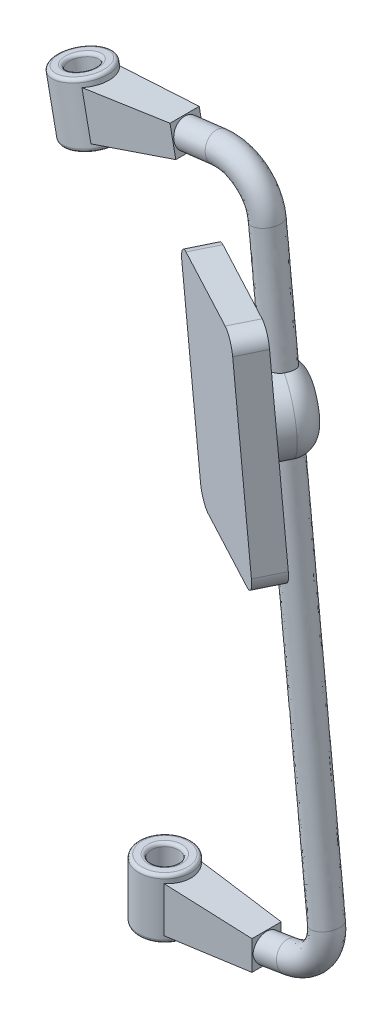
SolidWorks part; units mm, degrees
ref_plane "Front Plane" through (0, 0, 0) normal (0, 0, 1) x (1, 0, 0)
ref_plane "Top Plane" through (0, 0, 0) normal (0, 1, 0) x (1, 0, 0)
ref_plane "Right Plane" through (0, 0, 0) normal (1, 0, 0) x (0, 0, -1)
sketch "Sketch1" plane through (0, 0, 0) normal (0, 1, 0) x (1, 0, 0)
  circle A0 centre (0, 0) radius 12.5
  circle A1 centre (0, 0) radius 24
  dimension "D1" = 25
  dimension "D2" = 48
extrude "Boss-Extrude1" add sketch "Sketch1" along normal mid plane 55 contours A1 | A0
fillet "Fillet1" radius 3 4 edges at (0, 27.5, 12.5) (0, 27.5, 24) (0, -27.5, 12.5) (0, -27.5, 24)
ref_plane "Plane1" through (15, 0, 0) normal (1, 0, 0) x (0, 0, -1)
sketch "Sketch4" plane through (15, 0, 0) normal (1, 0, 0) x (0, 0, -1)
  line L0 (-20.6117, 0) -> (41.9806, 0) construction
  line L1 (0, 23.0094) -> (0, -24.2714) construction
  line L3 (-17.5, 21) -> (17.5, 21)
  line L4 (-17.5, 21) -> (-17.5, -21)
  line L5 (-17.5, -21) -> (17.5, -21)
  line L6 (17.5, 21) -> (17.5, -21)
  circle A0 centre (0, 0) radius 12.5
  dimension "D1" = 25
  dimension "D2" = 42
  dimension "D3" = 35
sketch "Sketch6" plane through (0, 0, 0) normal (0, 0, 1) x (1, 0, 0)
  line L0 (94, 0) -> (-270.3195, 0) construction
  line L1 (0, -79.4187) -> (0, 200.8809) construction
  line L2 (-40, -137.5526) -> (-40, 194) construction
  line L3 (-40, 194) -> (-114.1897, 559.2311) construction
  line L4 (-40, 194) -> (-40, 202.5264) construction
  line L6 (15.5, 27.5) -> (-15.5, 27.5) construction
  line L7 (-65.6804, 569.0848) -> (-65.6804, 254.5249) construction
  line L8 (-114.1897, 559.2311) -> (-65.6804, 569.0848) construction
  line L9 (24, -24.5) -> (24, 24.5) construction
  line L10 (-206.2715, 568.588) -> (20.964, 614.7466) construction
  line L11 (-65.6804, 569.0848) -> (-84.3739, 661.1117) construction
  dimension "D1" = 40
  dimension "D2" = 372.69
  dimension "D3" = 11.482
  dimension "D4" = 166.5
  dimension "D5" = 49.5
  dimension "D6" = 70
  dimension "D7" = 27.5
  dimension "D8" = 94
  dimension "D9" = 94
ref_plane "Plane2" through (-65.6804, 569.0848, 0) normal (-0.1991, 0.98, 0) x (0.98, 0.1991, 0)
sketch "Sketch8" plane through (-65.6804, 569.0848, 0) normal (-0.1991, 0.98, 0) x (0.98, 0.1991, 0)
  circle A0 centre (0, 0) radius 24
  circle A1 centre (0, 0) radius 12.5
  dimension "D1" = 25
  dimension "D2" = 48
extrude "Boss-Extrude2" add sketch "Sketch8" along normal blind 55 separate body
fillet "Fillet2" radius 3 4 edges at (-100.1487, 618.2065, 0) (-88.8788, 620.4957, 0) (-89.2001, 564.3072, 0) (-77.9302, 566.5965, 0)
ref_plane "Plane3" through (94, 0, 0) normal (1, 0, 0) x (0, 0, -1)
sketch "Sketch11" plane through (94, 0, 0) normal (1, 0, 0) x (0, 0, -1)
  line L0 (-26.258, 0) -> (32.0372, 0) construction
  line L1 (-13.5, 13.5) -> (13.5, 13.5)
  line L2 (-13.5, 13.5) -> (-13.5, -13.5)
  line L3 (-13.5, -13.5) -> (13.5, -13.5)
  line L4 (13.5, 13.5) -> (13.5, -13.5)
  line L5 (0, 21.6136) -> (0, -31.9549) construction
  line L6 (0, -137.5526) -> (0, 194) construction
  dimension "D1" = 27
  dimension "D2" = 27
loft "Loft1" add section "Sketch4" section "Sketch11"
ref_plane "Plane4" through (47.9402, 9.7381, 0) normal (0.98, 0.1991, 0) x (0, 0, -1)
ref_plane "Plane5" through (62.64, 12.7241, 0) normal (0.98, 0.1991, 0) x (0, 0, -1)
sketch "Sketch14" plane through (62.64, 12.7241, 0) normal (0.98, 0.1991, 0) x (0, 0, -1)
  line L0 (-40.0874, 598.2699) -> (54.1514, 598.2699) construction
  line L1 (0, 629.9205) -> (0, 567.8792) construction
  line L4 (24, 622.7699) -> (-24, 622.7699) construction
  line L5 (-24, 573.7699) -> (24, 573.7699) construction
  line L6 (-24, 622.7699) -> (-24, 573.7699) construction
  line L7 (24, 573.7699) -> (24, 622.7699) construction
  line L9 (-17.5, 619.2699) -> (17.5, 619.2699)
  line L10 (-17.5, 619.2699) -> (-17.5, 577.2699)
  line L11 (-17.5, 577.2699) -> (17.5, 577.2699)
  line L12 (17.5, 619.2699) -> (17.5, 577.2699)
  circle A0 centre (0, 598.2699) radius 12.5
  dimension "D1" = 25
  dimension "D2" = 42
  dimension "D3" = 35
ref_plane "Plane6" through (20.964, 614.7466, 0) normal (0.98, 0.1991, 0) x (0, 0, -1)
sketch "Sketch15" plane through (20.964, 614.7466, 0) normal (0.98, 0.1991, 0) x (0, 0, -1)
  line L1 (-13.5, 13.5) -> (13.5, 13.5)
  line L2 (-13.5, 13.5) -> (-13.5, -13.5)
  line L3 (-13.5, -13.5) -> (13.5, -13.5)
  line L4 (13.5, 13.5) -> (13.5, -13.5)
  line L5 (-40.0874, 0) -> (54.1514, 0) construction
  line L6 (0, 18.0247) -> (0, -17.7591) construction
  line L7 (0, -27.5) -> (0, 66.4063) construction
  dimension "D1" = 27
  dimension "D2" = 27
loft "Loft2" add section "Sketch14" section "Sketch15"
sketch "Sketch16" plane through (0, 0, 0) normal (0, 0, 1) x (1, 0, 0)
  line L0 (20.964, 614.7466) -> (50.0307, 618.2474)
  line L1 (94.6061, 582.6051) -> (149.3849, 47.1347)
  line L3 (116.018, 3.5834) -> (94, 0)
  arc A0 (50.0307, 618.2474) -> (94.6061, 582.6051) centre (54.8138, 578.5344) cw
  arc A1 (149.3849, 47.1347) -> (116.018, 3.5834) centre (109.5926, 43.0639) cw
  point P16 (90.4617, 623.1169)
  point P19 (153.2208, 9.6381)
  dimension "D3" = 40
  dimension "D1" = 70
  dimension "D2" = 60
sketch "Sketch17" plane through (140.0589, 28.4503, 0) normal (0.98, 0.1991, 0) x (0, 0, -1)
  circle A0 centre (0, 598.2699) radius 12.5
  dimension "D1" = 25
sweep "Sweep2" add profiles "Sketch17" path "Sketch16"
sketch "Sketch18" plane through (0, 0, 0) normal (0, 0, 1) x (1, 0, 0)
  line L0 (84.3257, 683.0971) -> (163.998, -95.7106) construction
  line L1 (161.6774, 49.4032) -> (106.8985, 584.8736) construction
  line L2 (82.3137, 580.3367) -> (137.0925, 44.8663) construction
ref_plane "Plane8" through (38.1524, 3.903, -66.4268) normal (-0.4974, -0.0509, 0.866) x (0.1018, -0.9948, 0)
sketch "Sketch20" plane through (38.1524, 3.903, -66.4268) normal (-0.4974, -0.0509, 0.866) x (0.1018, -0.9948, 0)
  line L0 (-670.9687, 132.8536) -> (111.9037, 132.8536) construction
  circle A0 centre (-426.664, 132.8536) radius 35
  dimension "D1" = 70
ref_plane "Plane7" through (15.7692, 1.6132, -27.4557) normal (-0.4974, -0.0509, 0.866) x (0.1018, -0.9948, 0)
extrude "Boss-Extrude5" add sketch "Sketch20" along normal mid plane 40 contours A0
sketch "Sketch19" plane through (15.7692, 1.6132, -27.4557) normal (-0.4974, -0.0509, 0.866) x (0.1018, -0.9948, 0)
  line L0 (-426.664, 132.8536) -> (-426.664, 343.4733) construction
  line L1 (-426.664, 343.4733) -> (-426.664, 640.0699) construction
  line L2 (0, 132.8536) -> (234.3011, 132.8536) construction
  line L4 (-511.664, 197.8536) -> (-341.664, 197.8536)
  line L5 (-526.664, 182.8536) -> (-526.664, 82.8536)
  line L6 (-511.664, 67.8536) -> (-341.664, 67.8536)
  line L7 (-326.664, 182.8536) -> (-326.664, 82.8536)
  line L8 (-670.9687, 132.8536) -> (111.9037, 132.8536) construction
  arc A0 (-526.664, 82.8536) -> (-511.664, 67.8536) centre (-511.664, 82.8536) ccw
  arc A1 (-341.664, 67.8536) -> (-326.664, 82.8536) centre (-341.664, 82.8536) ccw
  arc A2 (-341.664, 197.8536) -> (-326.664, 182.8536) centre (-341.664, 182.8536) cw
  arc A3 (-511.664, 197.8536) -> (-526.664, 182.8536) centre (-511.664, 182.8536) ccw
  point P14 (-326.664, 67.8536)
  point P17 (-326.664, 197.8536)
  point P20 (-526.664, 197.8536)
  dimension "D3" = 15
  dimension "D1" = 200
  dimension "D2" = 130
fillet "Fillet3" radius 20 1 edges at (149.4867, 441.0785, 0.1112)
extrude "Boss-Extrude6" add sketch "Sketch19" against normal up to surface (25 mm away) up to face at (129.5906, 439.0431, 34.7522)
